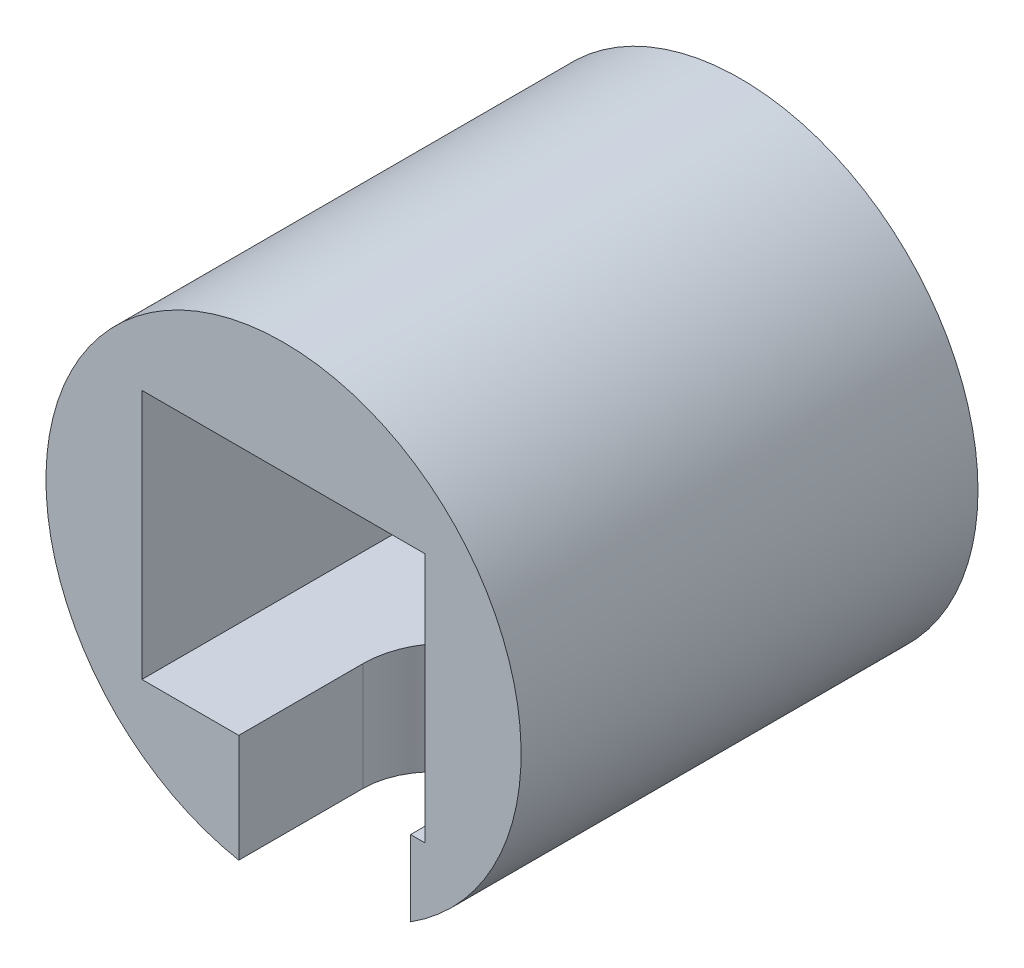
SolidWorks part; units mm, degrees
ref_plane "Front Plane" through (0, 0, 0) normal (0, 0, 1) x (1, 0, 0)
ref_plane "Top Plane" through (0, 0, 0) normal (0, 1, 0) x (1, 0, 0)
ref_plane "Right Plane" through (0, 0, 0) normal (1, 0, 0) x (0, 0, -1)
sketch "Sketch1" plane through (0, 0, 0) normal (0, 0, 1) x (1, 0, 0)
  circle A0 centre (0, 0) radius 3
  circle A1 centre (0, 0) radius 13
extrude "Boss-Extrude1" add sketch "Sketch1" along normal blind 25
sketch "Sketch2" plane through (0, 0, 0) normal (0, 1, 0) x (1, 0, 0)
  line L4 (7.75, -25) -> (-7.75, -25)
  line L11 (-7.75, -25) -> (-7.75, -11.2237)
  line L12 (7.75, -25) -> (7.75, -7.318)
  arc A3 (-7.75, -11.2237) -> (7.75, -7.318) centre (2.25, -18.2) cw
extrude "Cut-Extrude1" cut sketch "Sketch2" against normal mid plane 13.7
sketch "Sketch3" plane through (0, 0, 0) normal (0, 1, 0) x (1, 0, 0)
  line L5 (-2.45, -18.2) -> (-2.45, -25)
  line L6 (-2.45, -25) -> (6.95, -25)
  line L7 (6.95, -18.2) -> (6.95, -25)
  arc A1 (6.95, -18.2) -> (-2.45, -18.2) centre (2.25, -18.2) ccw
extrude "Cut-Extrude2" cut sketch "Sketch3" against normal up to surface (10.9862 mm away) up to face at (13, 0, 25)
